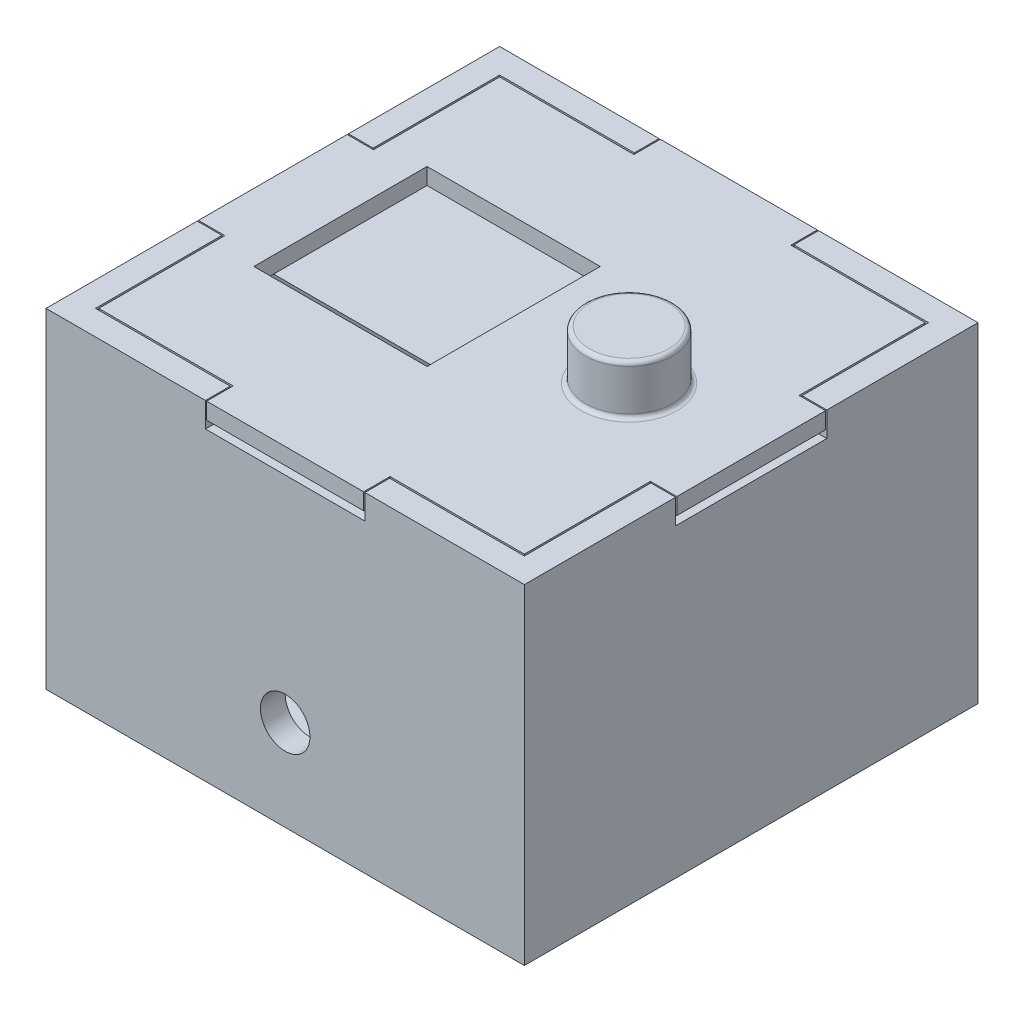
SolidWorks part; units mm, degrees
ref_plane "Front Plane" through (0, 0, 0) normal (0, 0, 1) x (1, 0, 0)
ref_plane "Top Plane" through (0, 0, 0) normal (0, 1, 0) x (1, 0, 0)
ref_plane "Right Plane" through (0, 0, 0) normal (1, 0, 0) x (0, 0, -1)
sketch "Sketch1" plane through (0, 0, 0) normal (0, 1, 0) x (1, 0, 0)
  line L1 (-29, 27.5) -> (29, 27.5)
  line L2 (-29, 27.5) -> (-29, -27.5)
  line L3 (-29, -27.5) -> (29, -27.5)
  line L4 (29, 27.5) -> (29, -27.5)
  line L5 (-29, 27.5) -> (29, -27.5) construction
  line L6 (-29, -27.5) -> (29, 27.5) construction
  point P0 (0, 0)
  dimension "D1" = 58
  dimension "D2" = 55
extrude "Boss-Extrude1" add sketch "Sketch1" along normal blind 40
shell "Shell1" thickness 3 removed face at (0, 40, 0)
sketch "Sketch2" plane through (29, 0, 0) normal (1, 0, 0) x (0, 0, -1)
  line L0 (-27.5, 40) -> (27.5, 40) construction
  line L1 (-9.1667, 40) -> (9.1667, 40)
  line L2 (-9.1667, 40) -> (-9.1667, 37)
  line L3 (-9.1667, 37) -> (9.1667, 37)
  line L4 (9.1667, 40) -> (9.1667, 37)
  point P4 (0, 40)
  point P7 (0, 40)
  dimension "D1" = 18.3333
  dimension "D2" = 3
extrude "Cut-Extrude1" cut sketch "Sketch2" against normal through all
sketch "Sketch3" plane through (0, 0, -27.5) normal (0, 0, -1) x (-1, 0, 0)
  line L0 (-29, 40) -> (29, 40) construction
  line L1 (-9.6667, 40) -> (9.6667, 40)
  line L2 (-9.6667, 40) -> (-9.6667, 37)
  line L3 (-9.6667, 37) -> (9.6667, 37)
  line L4 (9.6667, 40) -> (9.6667, 37)
  point P6 (0, 40)
  point P7 (0, 40)
  dimension "D1" = 19.3333
  dimension "D2" = 3
extrude "Cut-Extrude2" cut sketch "Sketch3" against normal through all
sketch "Sketch4" plane through (0, 0, -27.5) normal (0, 0, -1) x (-1, 0, 0)
  line L0 (9.6667, 40) -> (29, 40) construction
  line L1 (-9.5167, 37) -> (9.5167, 37)
  line L2 (-9.5167, 37) -> (-9.5167, 40)
  line L3 (-9.5167, 40) -> (9.5167, 40)
  line L4 (9.5167, 37) -> (9.5167, 40)
  line L5 (-9.6667, 40) -> (-9.6667, 37) construction
  line L6 (9.6667, 37) -> (9.6667, 40) construction
  line L8 (-9.6667, 37) -> (9.6667, 37) construction
  dimension "D1" = 0.15
  dimension "D2" = 0.15
extrude "Boss-Extrude2" add sketch "Sketch4" against normal through all separate body
sketch "Sketch5" plane through (-29, 0, 0) normal (-1, 0, 0) x (0, 0, 1)
  line L0 (9.1667, 40) -> (27.5, 40) construction
  line L1 (-9.0167, 37) -> (9.0167, 37)
  line L2 (-9.0167, 37) -> (-9.0167, 40)
  line L3 (-9.0167, 40) -> (9.0167, 40)
  line L4 (9.0167, 37) -> (9.0167, 40)
  line L5 (-9.1667, 37) -> (-9.1667, 40) construction
  line L6 (9.1667, 40) -> (9.1667, 37) construction
  line L8 (9.1667, 37) -> (-9.1667, 37) construction
  dimension "D1" = 0.15
  dimension "D2" = 0.15
extrude "Boss-Extrude3" add sketch "Sketch5" against normal through all
sketch "Sketch6" plane through (0, 40, 0) normal (0, 1, 0) x (1, 0, 0)
  line L0 (-26, 24.5) -> (-26, -24.5) construction
  line L1 (-25.8, 24.3) -> (25.8, 24.3)
  line L2 (-25.8, 24.3) -> (-25.8, -24.3)
  line L3 (-25.8, -24.3) -> (25.8, -24.3)
  line L4 (25.8, 24.3) -> (25.8, -24.3)
  line L5 (-25.8, 24.3) -> (25.8, -24.3) construction
  line L6 (-25.8, -24.3) -> (25.8, 24.3) construction
  line L7 (26, 24.5) -> (9.6667, 24.5) construction
  point P0 (0, 0)
  dimension "D1" = 0.2
  dimension "D2" = 0.2
extrude "Boss-Extrude4" add sketch "Sketch6" against normal blind 3
sketch "Sketch7" plane through (0, 40, 0) normal (0, 1, 0) x (1, 0, 0)
  line L0 (-25.8, 24.3) -> (-25.8, 9.0167) construction
  line L1 (-20.8, 10.5) -> (0.2, 10.5)
  line L2 (-20.8, 10.5) -> (-20.8, -10.5)
  line L3 (-20.8, -10.5) -> (0.2, -10.5)
  line L4 (0.2, 10.5) -> (0.2, -10.5)
  line L5 (-20.8, 10.5) -> (0.2, -10.5) construction
  line L6 (-20.8, -10.5) -> (0.2, 10.5) construction
  point P0 (-10.3, 0)
  dimension "D1" = 21
  dimension "D2" = 21
  dimension "D3" = 5
extrude "Cut-Extrude3" cut sketch "Sketch7" against normal blind 2
sketch "Sketch8" plane through (0, 38, 0) normal (0, 1, 0) x (1, 0, 0)
  line L0 (0.2, -10.5) -> (0.2, 10.5) construction
  line L1 (-20.8, -10.5) -> (0.2, -10.5)
  line L2 (-20.8, -10.5) -> (-20.8, -8.1)
  line L3 (-20.8, -8.1) -> (0.2, -8.1)
  line L4 (0.2, -10.5) -> (0.2, -8.1)
  dimension "D1" = 2.4
extrude "Cut-Extrude4" cut sketch "Sketch8" against normal up to next (1 mm away)
sketch "Sketch9" plane through (0, 40, 0) normal (0, 1, 0) x (1, 0, 0)
  line L0 (0.2, -8.1) -> (0.2, 10.5) construction
  circle A0 centre (14.2, 0) radius 4.3
  dimension "D1" = 8.6
  dimension "D2" = 14
extrude "Cut-Extrude5" cut sketch "Sketch9" against normal up to next (3 mm away)
sketch "Sketch10" plane through (0, 0, -27.5) normal (0, 0, -1) x (-1, 0, 0)
  line L1 (-5, 8) -> (5, 8)
  line L2 (-5, 8) -> (-5, 14)
  line L3 (-5, 14) -> (5, 14)
  line L4 (5, 8) -> (5, 14)
  line L5 (-29, 0) -> (29, 0) construction
  point P6 (0, 8)
  dimension "D1" = 14
  dimension "D2" = 6
  dimension "D3" = 10
extrude "Cut-Extrude6" cut sketch "Sketch10" against normal up to next (3 mm away)
sketch "Sketch11" plane through (0, 0, 24.5) normal (0, 0, -1) x (-1, 0, 0)
  line L0 (0, 14) -> (0, 8) construction
  line L1 (5, 14) -> (-5, 14) construction
  line L2 (-5, 8) -> (5, 8) construction
  circle A0 centre (0, 11) radius 3
  dimension "D1" = 6
extrude "Cut-Extrude7" cut sketch "Sketch11" against normal through all
sketch "Sketch12" plane through (0, 40, 0) normal (0, 1, 0) x (1, 0, 0)
  circle A0 centre (14.2, 0) radius 4.3 construction
  circle A1 centre (14.2, 0) radius 4.3
  circle A2 centre (14.2, 0) radius 5.3
  dimension "D1" = 1
extrude "Boss-Extrude5" add sketch "Sketch12" along normal blind 5
sketch "Sketch13" plane through (0, 45, 0) normal (0, 1, 0) x (1, 0, 0)
  circle A2 centre (14.2, 0) radius 5.3 construction
  circle A3 centre (14.2, 0) radius 5.3
extrude "Boss-Extrude6" add sketch "Sketch13" along normal blind 1
sketch "Sketch14" plane through (0, 46, 0) normal (0, 1, 0) x (1, 0, 0)
  circle A0 centre (14.2, 0) radius 1.5
  dimension "D1" = 3
fillet "Fillet1" radius 0.5 2 edges at (14.2, 46, 5.3) (14.2, 40, 5.3)
chamfer "Chamfer1" distance 1 angle 45 25 edges at (0, 37, -27.5) (-9.5167, 37, -25.9) (-17.6583, 37, -24.3) (-25.8, 37, -16.6583) (-27.4, 37, -9.0167) (-29, 37, 0) (-27.4, 37, 9.0167) (-25.8, 37, 16.6583) (-17.6583, 37, 24.3) (-9.5167, 37, 25.9) (0, 37, 27.5) (9.5167, 37, 25.9) (17.6583, 37, 24.3) (25.8, 37, 16.6583) (27.4, 37, 9.0167) (29, 37, 0) (27.4, 37, -9.0167) (25.8, 37, -16.6583) (17.6583, 37, -24.3) (9.5167, 37, -25.9) (-10.3, 37, 8.1) (0.2, 37, 9.3) (-10.3, 37, 10.5) (-20.8, 37, 9.3) (14.2, 37, -4.3)
equation "\"D1@Sketch3\"=58/3"
equation "\"Tab Tolerance\"= 0.15"
equation "\"Side Tolerance\"= 0.2"
equation "\"Motion Senso Hole\"= 8.6"
equation "\"RGB Sensor\"= 21"
equation "\"Header Length\"= 15.4"
equation "\"Header Thick\"= 2.4"
equation "\"D1@Sketch4\"=\"Tab Tolerance\""
equation "\"D2@Sketch4\"=\"Tab Tolerance\""
equation "\"D1@Sketch5\"=\"Tab Tolerance\""
equation "\"D2@Sketch5\"=\"Tab Tolerance\""
equation "\"D1@Sketch6\"=\"Side Tolerance\""
equation "\"D2@Sketch6\"=\"Side Tolerance\""
equation "\"D1@Sketch7\"=\"RGB Sensor\""
equation "\"D2@Sketch7\"=\"RGB Sensor\""
equation "\"D1@Sketch8\"=\"Header Thick\""
equation "\"D1@Sketch9\"=\"Motion Senso Hole\""
